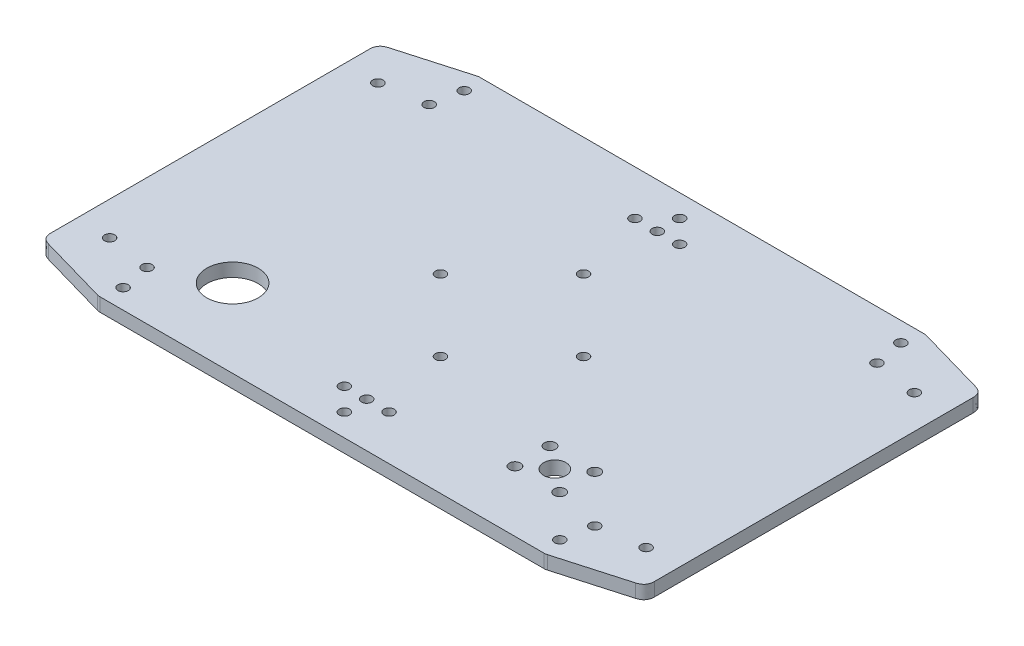
SolidWorks part; units mm, degrees
ref_plane "Plan de face" through (0, 0, 0) normal (0, 0, 1) x (1, 0, 0)
ref_plane "Plan de dessus" through (0, 0, 0) normal (0, 1, 0) x (1, 0, 0)
ref_plane "Plan de droite" through (0, 0, 0) normal (1, 0, 0) x (0, 0, -1)
sketch "Esquisse1" plane through (0, 0, 0) normal (0, 1, 0) x (1, 0, 0)
  line L0 (0, 0) -> (135, 0) construction
  line L1 (0, 0) -> (-135, 0) construction
  line L2 (-135, 0) -> (-135, -75)
  line L3 (-135, -85) -> (135, -85) construction
  line L4 (135, 0) -> (135, 75)
  line L5 (0, 85) -> (0, -85) construction
  line L6 (135, 85) -> (-135, 85) construction
  line L24 (0, -85) -> (-100, -85)
  line L26 (0, -85) -> (100, -85)
  line L28 (135, 0) -> (135, -75)
  line L31 (0, 85) -> (-100, 85)
  line L32 (0, 85) -> (100, 85)
  line L34 (-135, 0) -> (-135, 75)
  line L35 (-135, -75) -> (-100, -85)
  line L37 (-135, 75) -> (-100, 85)
  line L38 (100, 85) -> (135, 75)
  line L39 (100, -85) -> (135, -75)
  dimension "D1" = 170
  dimension "D2" = 200
  dimension "D3" = 170
extrude "Boss.-Extru.1" add sketch "Esquisse1" along normal blind 6
sketch "Esquisse15" plane through (0, 6, 0) normal (0, 1, 0) x (1, 0, 0)
  line L0 (-135, 60) -> (-135, 75)
  line L1 (-135, 60) -> (-120, 60) construction
  line L2 (-135, -60) -> (-120, -60) construction
  line L4 (-135, -60) -> (-135, -75)
  line L5 (-100, 85) -> (-135, 75) construction
  line L6 (-135, 75) -> (-135, -75) construction
  circle A0 centre (-120, 60) radius 2.3
  circle A1 centre (-120, -60) radius 2.3
extrude "Enlèv. mat.-Extru.6" cut sketch "Esquisse15" against normal up to next contours A1 | A0 region at (-120, 6, 60)
mirror "Symétrie5" about plane through (0, 0, 0) normal (1, 0, 0) of "Enlèv. mat.-Extru.6"
sketch "Esquisse17" plane through (0, 6, 0) normal (0, 1, 0) x (1, 0, 0)
  line L0 (0, -85) -> (0, -65) construction
  line L1 (-100, -85) -> (100, -85) construction
  line L4 (0, -65) -> (-10, -65) construction
  line L5 (0, -85) -> (0, -75) construction
  circle A0 centre (0, -65) radius 2.3
  circle A3 centre (10, -65) radius 2.3
  circle A5 centre (-10, -65) radius 2.3
  circle A6 centre (0, -75) radius 2.3
  dimension "D1" = 2
  dimension "D2" = 20
  dimension "D3" = 10
  dimension "D4" = 10
extrude "Enlèv. mat.-Extru.7" cut sketch "Esquisse17" against normal up to next
fillet "Congé3" radius 5 8 edges at (-135, 3, -75) (-100, 3, -85) (100, 3, -85) (135, 3, -75) (135, 3, 75) (100, 3, 85) (-100, 3, 85) (-135, 3, 75) second distance 5 conic rho 0.5 first distance on face at (-117.5, 3, -80) first distance on face at (0, 3, -85) first distance on face at (117.5, 3, -80) first distance on face at (135, 3, 0) first distance on face at (117.5, 3, 80) first distance on face at (0, 3, 85) first distance on face at (-117.5, 3, 80) first distance on face at (-135, 3, 0)
sketch "Esquisse19" plane through (0, 6, 0) normal (0, 1, 0) x (1, 0, 0)
  line L0 (-135, -50) -> (-135, 50) construction
  line L1 (-135, 71.2285) -> (-135, -71.2285) construction
  line L2 (-135, 50) -> (-75, 50) construction
  line L3 (-3.3275, 0) -> (3.3275, 0) construction
  line L4 (-135, -50) -> (-75, -50) construction
  circle A0 centre (-75, 50) radius 11.5 construction
  circle A1 centre (-75, -50) radius 11.5
  point P10 (-135, 0)
  dimension "D1" = 60
  dimension "D2" = 50
extrude "Enlèv. mat.-Extru.9" cut sketch "Esquisse19" against normal up to next
sketch "Esquisse20" plane through (0, 6, 0) normal (0, 1, 0) x (1, 0, 0)
  line L0 (0, 0) -> (0, 32) construction
  line L1 (0, 0) -> (0, -32) construction
  line L2 (0, 0) -> (32, 0) construction
  line L3 (0, 0) -> (-32, 0) construction
  circle A0 centre (0, 0) radius 40 construction
  circle A1 centre (-32, 0) radius 2.3
  circle A2 centre (0, -32) radius 2.3
  circle A3 centre (32, 0) radius 2.3
  circle A4 centre (0, 32) radius 2.3
extrude "Enlèv. mat.-Extru.10" cut sketch "Esquisse20" against normal up to next
sketch "Esquisse21" plane through (0, 6, 0) normal (0, 1, 0) x (1, 0, 0)
  line L0 (99.2997, -85) -> (99.2997, 50) construction
  line L1 (99.2997, 50) -> (69.1597, 50) construction
  line L2 (69.1597, 42.15) -> (69.1597, 57.85) construction
  line L3 (59.1597, 57.85) -> (79.1597, 57.85) construction
  line L4 (59.1597, 42.15) -> (79.1597, 42.15) construction
  line L5 (-3.3275, 0) -> (3.3275, 0) construction
  line L6 (59.1597, -42.15) -> (79.1597, -42.15) construction
  line L7 (59.1597, -57.85) -> (79.1597, -57.85) construction
  line L8 (69.1597, -42.15) -> (69.1597, -57.85) construction
  line L9 (99.2997, -50) -> (69.1597, -50) construction
  line L10 (99.2997, 85) -> (99.2997, -50) construction
  circle A0 centre (69.1597, 50) radius 5 construction
  circle A1 centre (79.1597, 57.85) radius 2.5 construction
  circle A2 centre (79.1597, 42.15) radius 2.5 construction
  circle A3 centre (59.1597, 57.85) radius 2.5 construction
  circle A4 centre (59.1597, 42.15) radius 2.5 construction
  circle A5 centre (59.1597, -42.15) radius 2.5
  circle A6 centre (59.1597, -57.85) radius 2.5
  circle A7 centre (79.1597, -42.15) radius 2.5
  circle A8 centre (79.1597, -57.85) radius 2.5
  circle A9 centre (69.1597, -50) radius 5
  dimension "D1" = 7.85
  dimension "D3" = 7.85
  dimension "D2" = 10
  dimension "D4" = 20
extrude "Enlèv. mat.-Extru.11" cut sketch "Esquisse21" against normal through all
sketch "Esquisse22" plane through (0, 6, 0) normal (0, 1, 0) x (1, 0, 0)
  line L0 (-94.4579, -81.3834) -> (-93.359, -77.5373) construction
  line L1 (-114.6499, -75.6142) -> (-94.4579, -81.3834) construction
  line L2 (-116.0235, -80.4219) -> (-114.6499, -75.6142) construction
  line L3 (-131.3736, -76.0361) -> (-100.6733, -84.8076) construction
  line L4 (-94.4579, -81.3834) -> (-88.9634, -62.1529) construction
  line L5 (-88.9634, -62.1529) -> (-103.3863, -58.0321) construction
  line L6 (-103.3863, -58.0321) -> (-104.4852, -61.8782) construction
  line L7 (-104.4852, -61.8782) -> (-95.8315, -64.3507) construction
  line L8 (-93.359, -77.5373) -> (-102.0127, -75.0648) construction
  circle A0 centre (-100.1583, -63.1144) radius 2.3
  circle A1 centre (-97.6858, -76.301) radius 2.3
  dimension "D2" = 20
  dimension "D6" = 9
  dimension "D1" = 15
  dimension "D3" = 4
  dimension "D4" = 90
  dimension "D5" = 9
  dimension "D7" = 21
  dimension "D8" = 5
  dimension "D9" = 90
  dimension "D10" = 90
  dimension "D11" = 90
  dimension "D12" = 4
  dimension "D13" = 4.5
extrude "Enlèv. mat.-Extru.12" cut sketch "Esquisse22" against normal up to next
mirror "Symétrie6" about plane through (0, 0, 0) normal (1, 0, 0) of "Enlèv. mat.-Extru.12"
mirror "Symétrie7" about plane through (0, 0, 0) normal (0, 0, 1) of "Enlèv. mat.-Extru.12", "Symétrie6"
mirror "Symétrie8" about plane through (0, 0, 0) normal (0, 0, 1) of "Enlèv. mat.-Extru.7"
